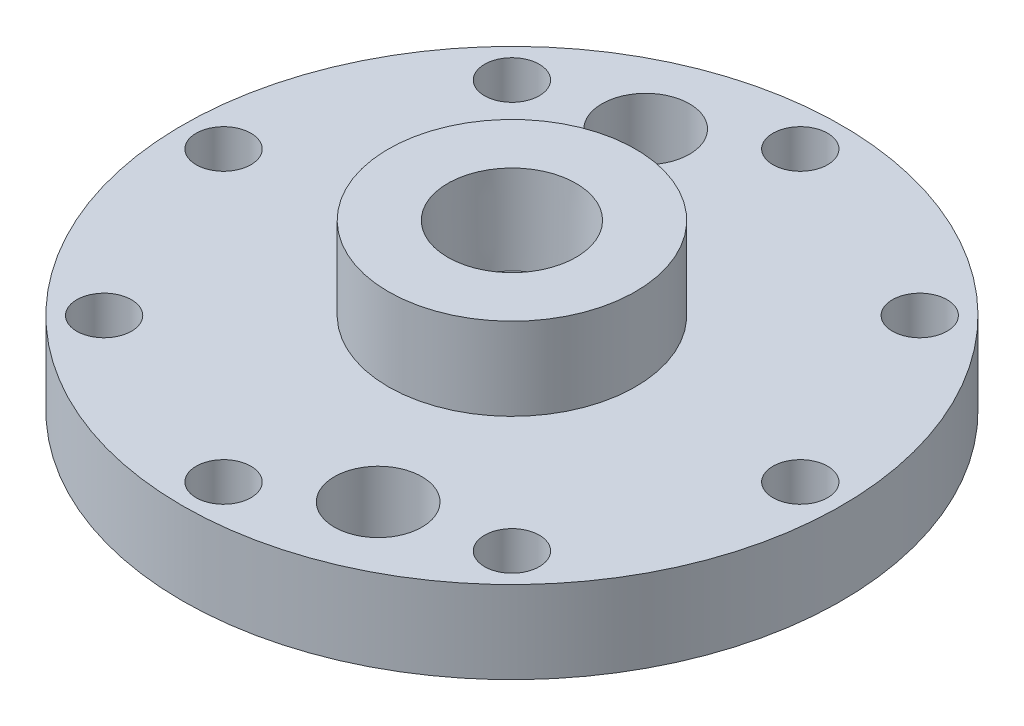
SolidWorks part; units mm, degrees
ref_plane "Front Plane" through (0, 0, 0) normal (0, 0, 1) x (1, 0, 0)
ref_plane "Top Plane" through (0, 0, 0) normal (0, 1, 0) x (1, 0, 0)
ref_plane "Right Plane" through (0, 0, 0) normal (1, 0, 0) x (0, 0, -1)
sketch "Sketch1" plane through (0, 0, 0) normal (0, 0, 1) x (1, 0, 0)
  line L0 (-19.431, 0) -> (-50.8, 0)
  line L1 (-50.8, 0) -> (-50.8, 12.7)
  line L2 (-50.8, 12.7) -> (-19.05, 12.7)
  line L3 (0, 25.4) -> (0, 0)
  line L4 (-19.431, 0) -> (-19.431, 2.54)
  line L5 (-19.431, 2.54) -> (-15.875, 2.54)
  line L6 (-15.875, 2.54) -> (-15.875, 0)
  line L7 (-15.875, 0) -> (0, 0)
  line L8 (0, 25.4) -> (-19.05, 25.4)
  line L9 (-19.05, 25.4) -> (-19.05, 12.7)
  dimension "D1" = 50.8
  dimension "D2" = 12.7
  dimension "D3" = 19.05
  dimension "D4" = 3.556
  dimension "D5" = 2.54
  dimension "D6" = 12.7
  dimension "D7" = 15.875
revolve "Revolve1" add sketch "Sketch1" angle 360 about L3
hole_wizard "1/2 NPT Tapped Hole1" positions "Sketch2" profile "Sketch4" size "1/2" standard "ANSI Inch" end condition through all
sketch "Sketch2" plane through (0, 25.4, 0) normal (0, 1, 0) x (1, 0, 0)
  point P0 (0, 0)
sketch "Sketch4" plane through (0, 25.4, 0) normal (1, 0, 0) x (0, 0, 1)
  line L0 (0, 0) -> (0, 25.4)
  line L1 (0, 25.4) -> (8.9281, 25.4)
  line L2 (-9.4797, 13.462) -> (-9.8828, 0) construction
  line L3 (8.9281, 25.4) -> (8.9281, 13.462)
  line L4 (8.9281, 13.462) -> (9.4797, 13.462)
  line L5 (9.4797, 13.462) -> (9.8828, 0)
  line L7 (9.8828, 0) -> (0, 0)
  line L8 (0, -6.35) -> (0, 107.95) construction
  line L11 (-8.9281, 13.462) -> (-9.4797, 13.462) construction
  dimension "Thru Tap Drill Dia." = 17.8562
  dimension "Thru Tap Drill Depth" = 25.4
  dimension "Thread Dia." = 19.7656
  dimension "Thread Angle" = 3.43
  dimension "Thread Depth" = 13.462
cosmetic thread "Hole Thread1" parameters "D1"=13.462, "D2"=21.3288
hole_wizard "5/16 Clearance Hole1" positions "Sketch5" profile "Sketch6" hole size "5/16" standard "ANSI Inch" end condition through all
sketch "Sketch5" plane through (0, 12.7, 0) normal (0, 1, 0) x (1, 0, 0)
  point P0 (44.45, 0)
  point P3 (0, 0)
  dimension "D1" = 44.45
sketch "Sketch6" plane through (44.45, 12.7, 0) normal (1, 0, 0) x (0, 0, 1)
  line L0 (0, 0) -> (0, 12.7)
  line L1 (0, 12.7) -> (4.2164, 12.7)
  line L2 (4.2164, 12.7) -> (4.2164, 0)
  line L5 (4.2164, 0) -> (0, 0)
  line L11 (0, -6.35) -> (0, 107.95) construction
  dimension "Thru Hole Dia." = 8.4328
  dimension "Thru Hole Depth" = 12.7
pattern_circular "CirPattern1" count 8 over 360 about axis through (0, 25.4, 0) along (0, 1, 0) of "5/16 Clearance Hole1" reverse direction yes
hole_wizard "1/2 Clearance Hole1" positions "Sketch7" profile "Sketch8" hole size "1/2" standard "ANSI Inch" end condition through all
sketch "Sketch7" plane through (0, 12.7, 0) normal (0, 1, 0) x (1, 0, 0)
  line L0 (0, 0) -> (-14.5802, 35.1998) construction
  line L2 (0, 0) -> (0, 30.2547) construction
  point P0 (-14.5802, 35.1998)
  dimension "D1" = 22.5
  dimension "D2" = 38.1
sketch "Sketch8" plane through (-14.5802, 12.7, -35.1998) normal (1, 0, 0) x (0, 0, 1)
  line L0 (0, 0) -> (0, 12.7)
  line L1 (0, 12.7) -> (6.7462, 12.7)
  line L2 (6.7462, 12.7) -> (6.7462, 0)
  line L5 (6.7462, 0) -> (0, 0)
  line L11 (0, -6.35) -> (0, 107.95) construction
  dimension "Thru Hole Dia." = 13.4925
  dimension "Thru Hole Depth" = 12.7
pattern_circular "CirPattern2" count 2 over 360 about axis through (0, 25.4, 0) along (0, 1, 0) of "1/2 Clearance Hole1"
